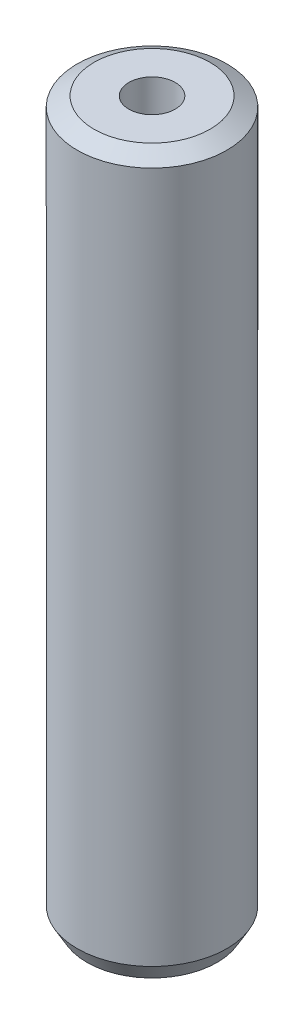
SolidWorks part; units mm, degrees
ref_plane "Front Plane" through (0, 0, 0) normal (0, 0, 1) x (1, 0, 0)
ref_plane "Top Plane" through (0, 0, 0) normal (0, 1, 0) x (1, 0, 0)
ref_plane "Right Plane" through (0, 0, 0) normal (1, 0, 0) x (0, 0, -1)
sketch "Sketch1" plane through (0, 0, 0) normal (0, 1, 0) x (1, 0, 0)
  circle A0 centre (0, 0) radius 37.5
  dimension "SHAFT_OD" = 75
extrude "Boss-Extrude1" add sketch "Sketch1" along normal blind 359.79
sketch "Sketch2" plane through (0, 0, 0) normal (0, 1, 0) x (1, 0, 0)
  circle A0 centre (0, 0) radius 11.619
  dimension "BORE_D" = 23.238
extrude "Cut-Extrude1" cut sketch "Sketch2" along normal through all
chamfer "Chamfer1" distance 4.8751 angle 60 2 edges at (0, 359.79, 37.5) (0, 0, 37.5) first distance on face at (0, 359.79, 37.5) first distance on face at (0, 0, 11.619)
